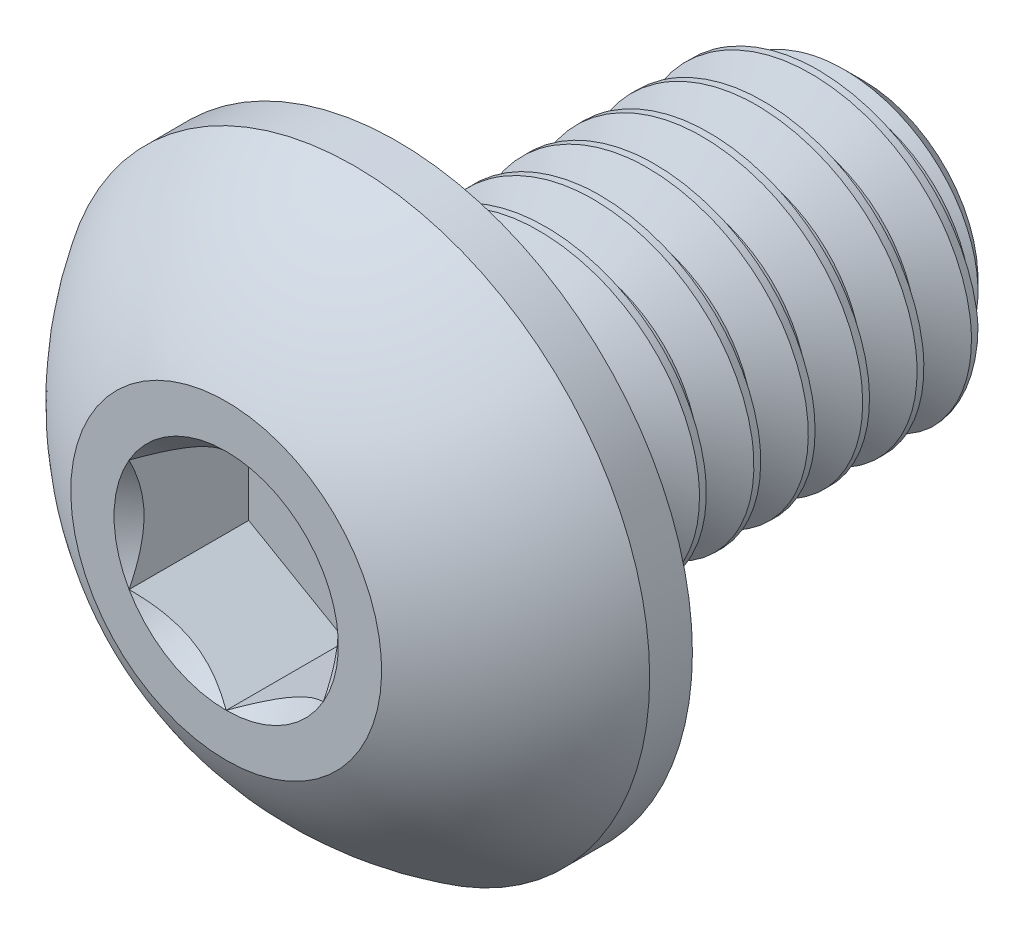
SolidWorks part; units mm, degrees
ref_plane "Front" through (0, 0, 0) normal (0, 0, 1) x (1, 0, 0)
ref_plane "Top" through (0, 0, 0) normal (0, 1, 0) x (1, 0, 0)
ref_plane "Right" through (0, 0, 0) normal (1, 0, 0) x (0, 0, -1)
sketch "Sketch1" plane through (0, 0, 0) normal (1, 0, 0) x (0, 0, -1)
  line L2 (2.2, 2) -> (8.2, 2)
  line L3 (8.2, 2) -> (8.2, 0)
  line L4 (8.2, 0) -> (2.2, 0)
  line L6 (1.65, 3.8) -> (2.2, 3.8) construction
  line L7 (8.2, 2) -> (8.2, -2) construction
  line L8 (0, 0) -> (2.2, 0) construction
  line L9 (2.2, 3.8) -> (2.2, -3.8) construction
  line L11 (2.2, 2) -> (2.2, 0)
  line L13 (0, 1.25) -> (0, -1.25) construction
  line L14 (0, 1.25) -> (0, 2) construction
  line L15 (1.65, 3.8) -> (1.65, 3.7703) construction
  line L16 (1.65, 3.7703) -> (2.2, 3.7703) construction
  line L17 (2.2, 3.7703) -> (2.2, 3.8) construction
  line L18 (2.2, 3.7703) -> (2.2, -3.7703) construction
  arc A3 (0, 2) -> (1.65, 3.8) centre (3.9886, 0) cw construction
  dimension "D1" = 0.55
revolve "Revolve1" add sketch "Sketch1" angle 360 mid plane about L4
sketch "Sketch3" plane through (0, 0, -8.2) normal (0, 0, -1) x (-1, 0, 0)
  circle A0 centre (0, 0) radius 2
curve "Helix/Spiral1" pitch 0.7 height 6.7 radius 2 centre (0, 0, -8.2) axis (0, 0, 1) start towards (0, 1, 0)
sketch "Sketch2" plane through (0, 0, 0) normal (1, 0, 0) x (0, 0, -1)
  line L0 (8.2, 2) -> (8.8125, 2)
  line L1 (8.8125, 2) -> (8.55, 1.5453)
  line L2 (8.55, 1.5453) -> (8.4625, 1.5453)
  line L3 (8.4625, 1.5453) -> (8.2, 2)
  line L4 (8.3313, 1.7727) -> (8.6813, 1.7727) construction
  dimension "D1" = 60
  dimension "D2" = 0.0875
  dimension "D3" = 0.35
chamfer "Chamfer1" distance 0.525 angle 45 1 edges at (0, 2, -8.2)
sweep "Cut-Sweep1" cut profiles "Sketch2" path "Helix/Spiral1" align with end faces yes
sketch "Sketch7" plane through (0, 0, 0) normal (1, 0, 0) x (0, 0, -1)
  line L6 (1.65, 3.8) -> (2.2, 3.8) construction
  line L8 (0, 0) -> (2.2, 0) construction
  line L11 (2.2, 3.8) -> (2.2, -3.8) construction
  line L12 (1.65, 3.8) -> (2.2, 3.8)
  line L13 (0, 0) -> (2.2, 0)
  line L14 (0, 1.25) -> (0, -1.25) construction
  line L15 (2.2, 3.8) -> (2.2, 0)
  line L16 (0, 2) -> (0, 0)
  arc A2 (1.65, 3.8) -> (0, 2) centre (3.9886, 0) ccw construction
  arc A3 (1.65, 3.8) -> (0, 2) centre (3.9886, 0) ccw
revolve "Revolve2" add sketch "Sketch7" angle 360 mid plane about L13
sketch "Sketch11" plane through (0, 0, -2.2) normal (0, 0, -1) x (-1, 0, 0)
  circle A0 centre (0, 0) radius 3.7703
sketch "Sketch5" plane through (0, 0, 0) normal (0, 0, 1) x (1, 0, 0)
  line L1 (1.25, -0.7217) -> (1.25, 0.7217)
  line L2 (1.25, 0.7217) -> (0, 1.4434)
  line L3 (0, 1.4434) -> (-1.25, 0.7217)
  line L4 (-1.25, 0.7217) -> (-1.25, -0.7217)
  line L5 (-1.25, -0.7217) -> (0, -1.4434)
  line L6 (0, -1.4434) -> (1.25, -0.7217)
  circle A0 centre (0, 0) radius 1.25 construction
extrude "Cut-Extrude2" cut sketch "Sketch5" against normal blind 1.54
sketch "Sketch6" plane through (0, 0, 0) normal (0, 0, 1) x (1, 0, 0)
  circle A0 centre (0, 0) radius 1.4434
extrude "Cut-Extrude3" cut sketch "Sketch6" against normal blind 1.54 draft 45
sketch "Sketch9" [suppressed] plane through (0, 0, -5.0546) normal (0, 0, 1) x (1, 0, 0)
  circle A2 centre (0, 0) radius 4.7625
extrude "Boss-Extrude2" [suppressed] add sketch "Sketch9" against normal offset from surface (6.35 mm away) 31.75 up to face at (0, 1.475, -8.2)
sketch "Sketch10" plane through (0, 0, 0) normal (1, 0, 0) x (0, 0, -1)
  line L0 (8.2, 2) -> (8.2, -2) construction
  point P0 (7.15, -2)
  dimension "D1" = 1.05
sketch "Sketch14" plane through (0, 0, -8.2) normal (0, 0, -1) x (-1, 0, 0)
  circle A0 centre (0, 0) radius 0.5842
  dimension "Hole" = 1.1684
extrude "Cut-Extrude6" cut sketch "Sketch14" against normal through all
equation "\"D3@Helix/Spiral1\" = \"Lg@Sketch1\" + \"D4@Helix/Spiral1\""
equation "\"D2@Sketch2\" = \"D4@Helix/Spiral1\" * .125"
equation "\"D3@Sketch2\" = \"D4@Helix/Spiral1\" * .5"
equation "\"D1@Chamfer1\" = \"D4@Helix/Spiral1\" * .75"
equation "\"D1@Cut-Extrude2\" = \"Head Ht@Sketch1\" * .7"
equation "\"D1@Sketch1\" = \"Head Ht@Sketch1\" * .25"
equation "\"D1@Sketch10\" = \"D4@Helix/Spiral1\" * 1.5"
equation "\"D1@Cut-Extrude3\" = \"D1@Cut-Extrude2\""
